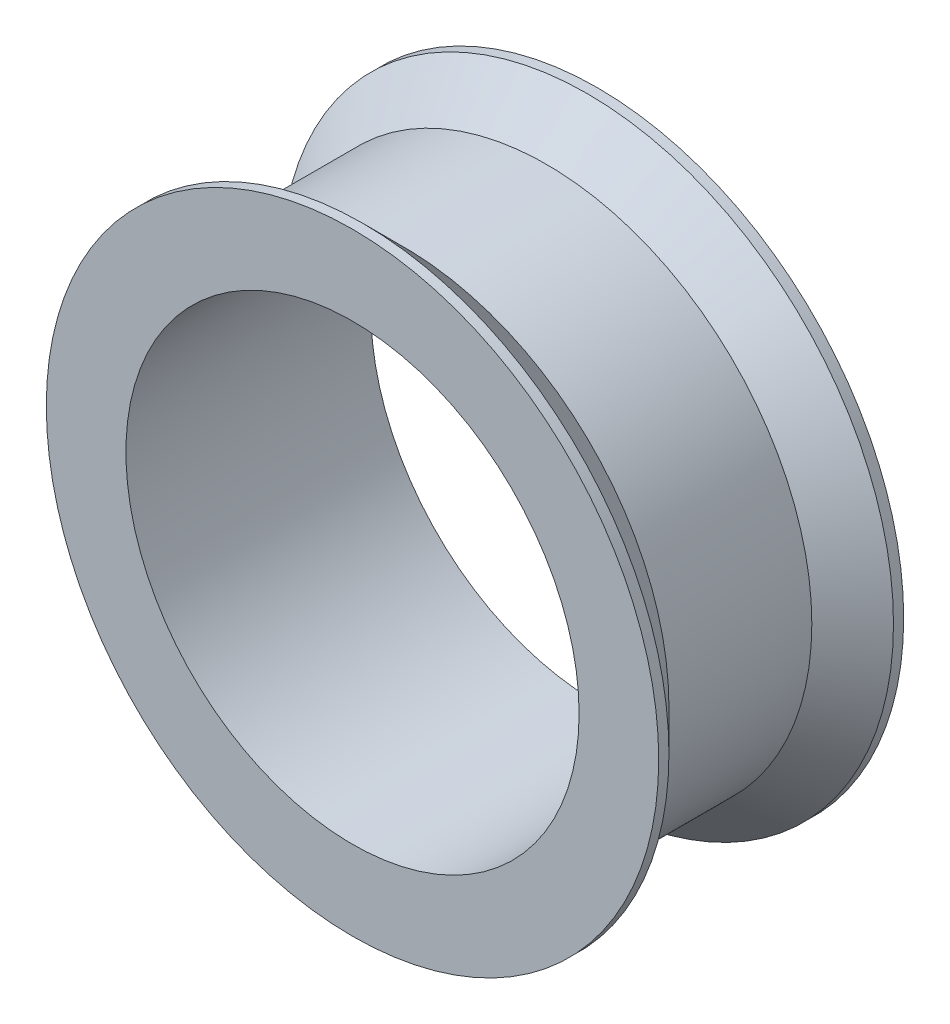
SolidWorks part; units mm, degrees
ref_plane "Front Plane" through (0, 0, 0) normal (0, 0, 1) x (1, 0, 0)
ref_plane "Top Plane" through (0, 0, 0) normal (0, 1, 0) x (1, 0, 0)
ref_plane "Right Plane" through (0, 0, 0) normal (1, 0, 0) x (0, 0, -1)
sketch "Sketch1" plane through (0, 0, 0) normal (0, 0, 1) x (1, 0, 0)
  circle A0 centre (0, 0) radius 11.1
  circle A1 centre (0, 0) radius 15
  circle A2 centre (0, 0) radius 13
  dimension "D1" = 22.2
  dimension "D2" = 26
  dimension "D3" = 30
extrude "Boss-Extrude1" add sketch "Sketch1" along normal mid plane 12 contours A2 A0 | A1 A2 region at (-14.5757, 0, 0) region at (-12.6323, 0, 0)
extrude "Cut-Extrude1" cut sketch "Sketch1<3>" against normal mid plane 7 contours A1 A2 region at (-14.5757, 0, 0)
sketch "Sketch1<3>" plane through (0, 0, 0) normal (0, 0, 1) x (1, 0, 0) same geometry as "Sketch1"
chamfer "Chamfer1" distance 2 angle 45 2 edges at (15, 0, 3.5) (15, 0, -3.5)
